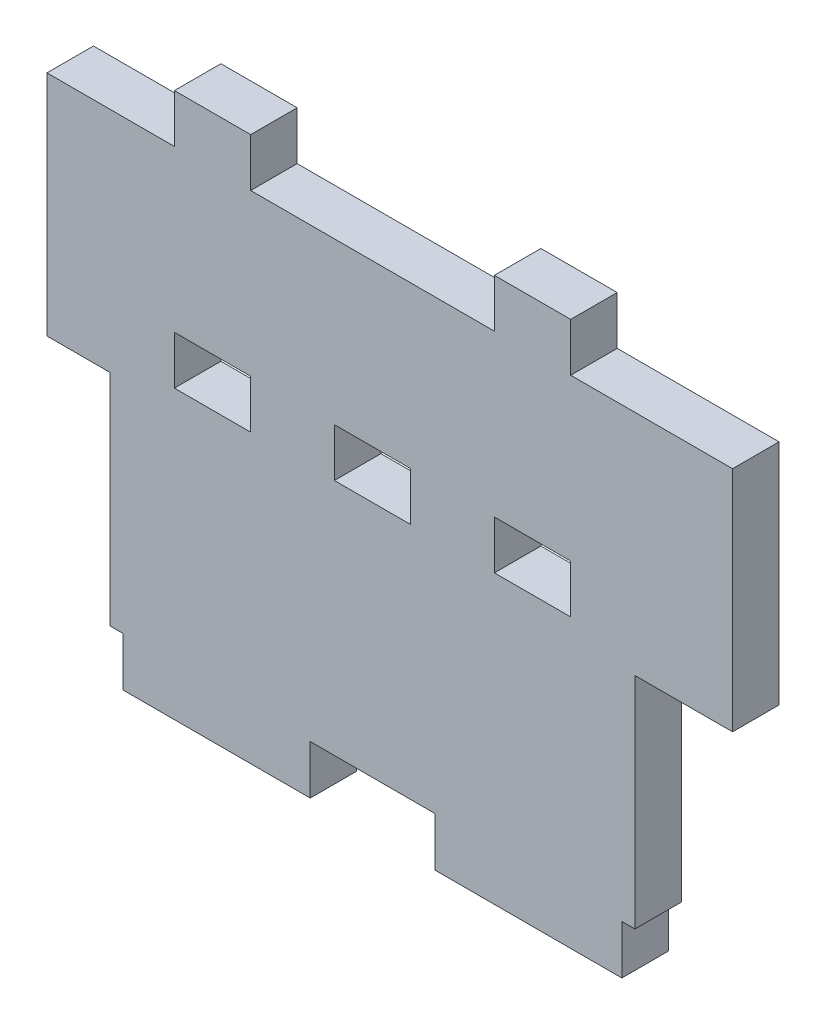
SolidWorks part; units mm, degrees
ref_plane "Front Plane" through (0, 0, 0) normal (0, 0, 1) x (1, 0, 0)
ref_plane "Top Plane" through (0, 0, 0) normal (0, 1, 0) x (1, 0, 0)
ref_plane "Right Plane" through (0, 0, 0) normal (1, 0, 0) x (0, 0, -1)
sketch "Sketch1" plane through (0, 0, 0) normal (0, 0, 1) x (1, 0, 0)
  line L0 (26.9176, -2.0915) -> (33.7176, -2.0915)
  line L1 (-36.2824, 22.4085) -> (33.7176, 22.4085)
  line L2 (-36.2824, 22.4085) -> (-36.2824, -2.0915)
  line L3 (-36.2824, -2.0915) -> (-29.4824, -2.0915)
  line L4 (33.7176, 22.4085) -> (33.7176, -2.0915)
  line L5 (-7.9824, -25.6915) -> (5.4176, -25.6915)
  line L6 (-29.4824, -2.0915) -> (-29.4824, -25.6915)
  line L7 (-29.4824, -25.6915) -> (-28.0824, -25.6915)
  line L8 (26.9176, -2.0915) -> (26.9176, -25.6915)
  line L9 (25.5176, -25.6915) -> (26.9176, -25.6915)
  line L10 (-28.0824, -25.6915) -> (-28.0824, -30.9557)
  line L11 (-28.0824, -30.9557) -> (-7.9824, -30.9557)
  line L12 (-7.9824, -25.6915) -> (-7.9824, -30.9557)
  line L14 (5.4176, -25.6915) -> (5.4176, -30.9557)
  line L15 (5.4176, -30.9557) -> (25.5176, -30.9557)
  line L16 (25.5176, -25.6915) -> (25.5176, -30.9557)
  dimension "D1" = 70
  dimension "D2" = 24.5
  dimension "D3" = 6.8
  dimension "D4" = 1.4
  dimension "D5" = 20.1
  dimension "D6" = 23.6
extrude "Boss-Extrude1" add sketch "Sketch1" along normal blind 5 contours L1 L4 L0 L8 L9 L16 L15 L14 L5 L12 L11 L10 L7 L6 L3 L2
sketch "Sketch2" plane through (0, 0, 5) normal (0, 0, 1) x (1, 0, 0)
  line L0 (-8.8824, 2.5085) -> (-36.2824, 2.5085) construction
  line L1 (-22.5824, 5.1085) -> (-14.3824, 5.1085)
  line L2 (-22.5824, 5.1085) -> (-22.5824, -0.0915)
  line L3 (-22.5824, -0.0915) -> (-14.3824, -0.0915)
  line L4 (-14.3824, 5.1085) -> (-14.3824, -0.0915)
  line L5 (-36.2824, 22.4085) -> (-36.2824, -2.0915) construction
  line L6 (33.7176, 22.4085) -> (33.7176, -2.0915) construction
  line L7 (-36.2824, -2.0915) -> (-29.4824, -2.0915) construction
  line L8 (-5.3824, 5.1085) -> (2.8176, 5.1085)
  line L9 (-5.3824, 5.1085) -> (-5.3824, -0.0915)
  line L10 (-5.3824, -0.0915) -> (2.8176, -0.0915)
  line L11 (2.8176, 5.1085) -> (2.8176, -0.0915)
  line L12 (-1.2824, 5.1085) -> (-1.2824, -0.0915) construction
  line L13 (11.8176, 5.1085) -> (20.0176, 5.1085)
  line L14 (11.8176, 5.1085) -> (11.8176, -0.0915)
  line L15 (11.8176, -0.0915) -> (20.0176, -0.0915)
  line L16 (20.0176, 5.1085) -> (20.0176, -0.0915)
  line L25 (8.3176, 2.5085) -> (-19.0824, 2.5085) construction
  line L26 (25.5176, 2.5085) -> (-1.8824, 2.5085) construction
  line L27 (42.7176, 2.5085) -> (15.3176, 2.5085) construction
  line L28 (29.0176, 5.1085) -> (37.2176, 5.1085) [skipped]
  line L29 (29.0176, 5.1085) -> (29.0176, -0.0915) [skipped]
  line L30 (29.0176, -0.0915) -> (37.2176, -0.0915) [skipped]
  line L31 (37.2176, 5.1085) -> (37.2176, -0.0915) [skipped]
  point P9 (-22.5824, 2.5085)
  point P11 (29.0176, 2.5085)
  point P18 (-5.3824, 2.5085)
  point P25 (11.8176, 2.5085)
  dimension "D3" = 5.2
  dimension "D4" = 4
  dimension "D5" = 9
  dimension "D6" = 35
  dimension "D1" = 4.6
  dimension "D2" = 8.2
extrude "Cut-Extrude1" cut sketch "Sketch2" against normal up to next
sketch "Sketch3" plane through (0, 0, 5) normal (0, 0, 1) x (1, 0, 0)
  line L0 (-36.2824, 22.4085) -> (33.7176, 22.4085) construction
  line L1 (33.7176, 22.4085) -> (37.4176, 22.4085)
  line L2 (33.7176, 22.4085) -> (33.7176, -2.0915)
  line L3 (33.7176, -2.0915) -> (37.4176, -2.0915)
  line L4 (37.4176, 22.4085) -> (37.4176, -2.0915)
  line L5 (26.9176, -2.0915) -> (33.7176, -2.0915) construction
  dimension "D1" = 3.7
extrude "Boss-Extrude4" add sketch "Sketch3" against normal blind 5
sketch "Sketch4" plane through (0, 0, 5) normal (0, 0, 1) x (1, 0, 0)
  line L0 (-36.2824, 22.4085) -> (37.4176, 22.4085) construction
  line L1 (-22.5824, 22.4085) -> (-14.3824, 22.4085)
  line L2 (-22.5824, 22.4085) -> (-22.5824, 27.6085)
  line L3 (-22.5824, 27.6085) -> (-14.3824, 27.6085)
  line L4 (-14.3824, 22.4085) -> (-14.3824, 27.6085)
  line L5 (-22.5824, 5.1085) -> (-22.5824, -0.0915) construction
  line L6 (11.8176, 22.4085) -> (20.0176, 22.4085)
  line L7 (11.8176, 22.4085) -> (11.8176, 27.6085)
  line L8 (11.8176, 27.6085) -> (20.0176, 27.6085)
  line L9 (20.0176, 22.4085) -> (20.0176, 27.6085)
  line L10 (-14.3824, -0.0915) -> (-14.3824, 5.1085) construction
  line L11 (11.8176, 5.1085) -> (11.8176, -0.0915) construction
  line L12 (20.0176, -0.0915) -> (20.0176, 5.1085) construction
extrude "Boss-Extrude7" add sketch "Sketch4" against normal up to surface (5 mm away) up to face at (15.9176, 2.5085, 0)
